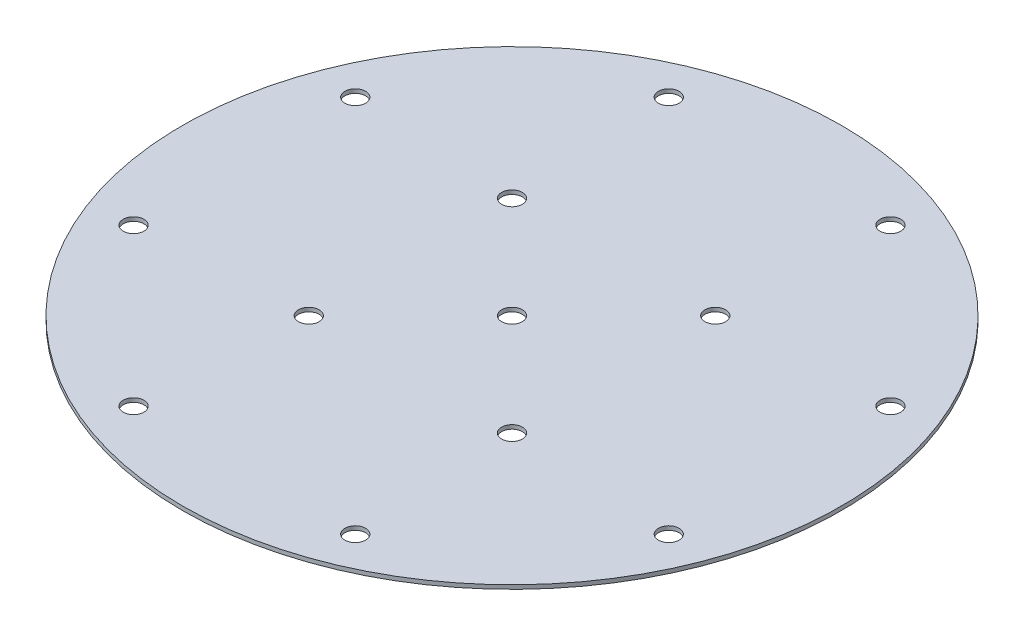
SolidWorks part; units mm, degrees
material "6061-T6 (SS)"
ref_plane "Front Plane" through (0, 0, 0) normal (0, 0, 1) x (1, 0, 0)
ref_plane "Top Plane" through (0, 0, 0) normal (0, 1, 0) x (1, 0, 0)
ref_plane "Right Plane" through (0, 0, 0) normal (1, 0, 0) x (0, 0, -1)
sketch "Sketch2" plane through (0, 0, 0) normal (1, 0, 0) x (0, 0, -1)
  line L0 (0, 0) -> (-82.55, 0)
  line L1 (-82.55, 0) -> (-82.55, 1)
  line L2 (-82.55, 1) -> (0, 1)
  line L5 (0, 1) -> (0, 0)
  dimension "D1" = 82.55
  dimension "D2" = 1
ref_axis "Axis1" through (0, -0.05, 0) along (0, 1, 0)
revolve "Revolve1" add sketch "Sketch2" angle 360 about axis through (0, -0.05, 0) along (0, 1, 0)
hole_wizard "#6 (0.204) Diameter Hole1" positions "Sketch6" profile "Sketch7" hole size "#6" standard "ANSI Inch" end condition through all
sketch "Sketch6" plane through (0, 1, 0) normal (0, 1, 0) x (1, 0, 0)
  line L0 (0, 0) -> (-53.438, 129.0108) construction
  line L2 (0, 0) -> (0, 109.0908) construction
  line L3 (0, 0) -> (-76.2663, 31.5905) construction
  line L4 (0, 0) -> (-47.7784, 47.7784) construction
  circle A0 centre (0, 0) radius 82.55 construction
  point P0 (-27.7637, 67.0275)
  point P11 (264.7437, 73.7878)
  point P20 (-67.0275, 27.7637)
  point P22 (-25.4558, 25.4558)
  dimension "D1" = 22.5
  dimension "D2" = 72.55
  dimension "D3" = 72.55
  dimension "D4" = 45
  dimension "D6" = 22.5
  dimension "D5" = 36
sketch "Sketch7" plane through (-27.7637, 1, -67.0275) normal (1, 0, 0) x (0, 0, 1)
  line L0 (0, 0) -> (0, 1)
  line L1 (0, 1) -> (2.5908, 1)
  line L2 (2.5908, 1) -> (2.5908, 0)
  line L5 (2.5908, 0) -> (0, 0)
  line L11 (0, -6.35) -> (0, 107.95) construction
  dimension "Thru Hole Dia." = 5.1816
  dimension "Thru Hole Depth" = 1
pattern_circular "CirPattern3" count 4 over 360 about axis through (0, -0.05, 0) along (0, 1, 0) of "#6 (0.204) Diameter Hole1"
hole_wizard "#6 (0.204) Diameter Hole2" positions "Sketch8" profile "Sketch9" hole size "#6" standard "ANSI Inch" end condition through all
sketch "Sketch8" plane through (0, 1, 0) normal (0, 1, 0) x (1, 0, 0)
  line L0 (0, 0) -> (106.3094, -1.7118) construction
  point P7 (0, 0)
sketch "Sketch9" plane through (0, 1, 0) normal (1, 0, 0) x (0, 0, 1)
  line L0 (0, 0) -> (0, 1)
  line L1 (0, 1) -> (2.5908, 1)
  line L2 (2.5908, 1) -> (2.5908, 0)
  line L5 (2.5908, 0) -> (0, 0)
  line L11 (0, -6.35) -> (0, 107.95) construction
  dimension "Thru Hole Dia." = 5.1816
  dimension "Thru Hole Depth" = 1
equation "\"TubeDiameter\" = 6.500in"
equation "\"D1@Sketch2\"=\"TubeDiameter\"/2"
equation "\"D2@Sketch6\"=\"TubeDiameter\"/2-10mm"
equation "\"D3@Sketch6\"=\"TubeDiameter\"/2-10mm"
